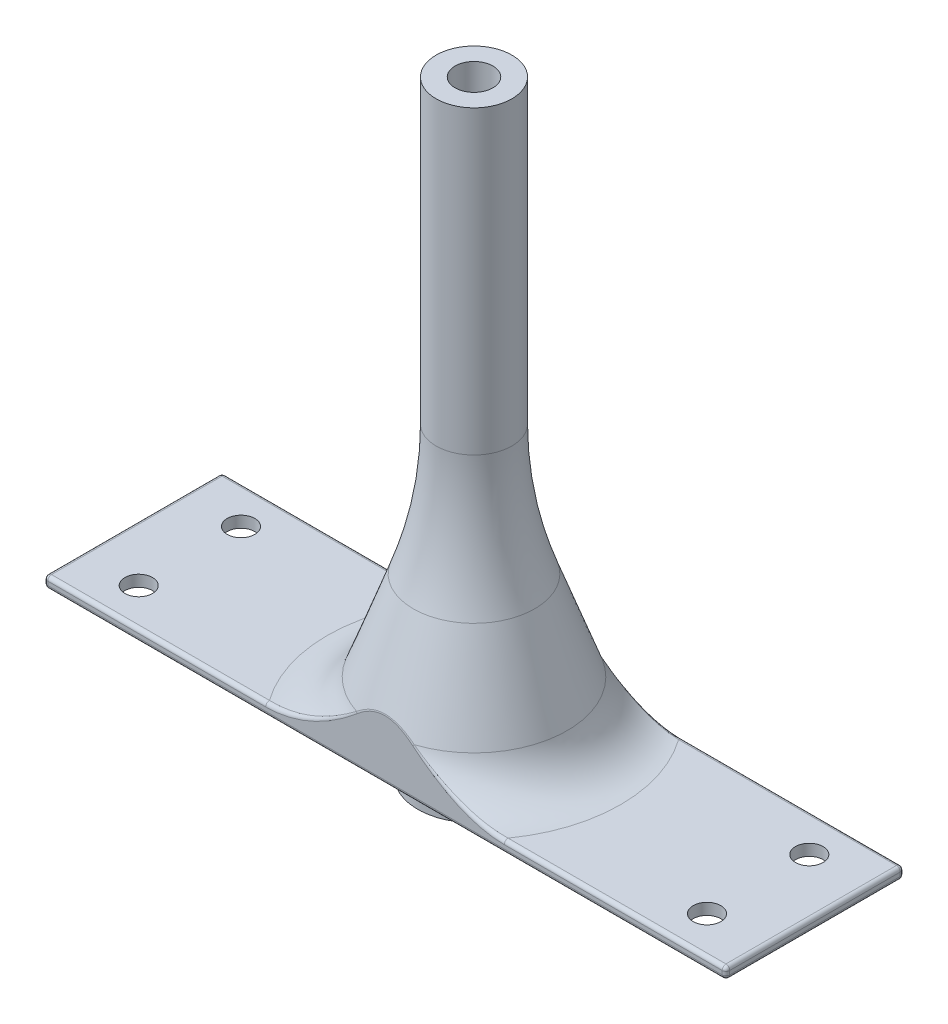
SolidWorks part; units mm, degrees
ref_plane "Alzado" through (0, 0, 0) normal (0, 0, 1) x (1, 0, 0)
ref_plane "Planta" through (0, 0, 0) normal (0, 1, 0) x (1, 0, 0)
ref_plane "Vista lateral" through (0, 0, 0) normal (1, 0, 0) x (0, 0, -1)
sketch "Croquis1" plane through (0, 0, 0) normal (0, 1, 0) x (1, 0, 0)
  circle A0 centre (0, 0) radius 10
  dimension "D1" = 20
extrude "Saliente-Extruir1" add sketch "Croquis1" along normal blind 150 and the other way blind 10
sketch "Croquis5" plane through (0, 150, 0) normal (0, -1, 0) x (1, 0, 0)
  circle A0 centre (0, 0) radius 5
  dimension "D1" = 10
extrude "Cortar-Extruir1" cut sketch "Croquis5" against normal through all both and the other way through all
sketch "Croquis6" plane through (0, 0, 0) normal (0, 1, 0) x (1, 0, 0)
  line L0 (-90, 13.5) -> (-75, 13.5) construction
  line L1 (-90, 23.5) -> (90, 23.5)
  line L2 (-90, 23.5) -> (-90, -23.5)
  line L3 (-90, -23.5) -> (90, -23.5)
  line L4 (90, 23.5) -> (90, -23.5)
  line L5 (-90, 23.5) -> (90, -23.5) construction
  line L6 (-90, -23.5) -> (90, 23.5) construction
  line L7 (-75, 13.5) -> (-75, 23.5) construction
  line L8 (-18.619, 0) -> (0, 0) construction
  line L9 (0, 0) -> (0, 19.4113) construction
  circle A0 centre (-75, 13.5) radius 3.65
  circle A1 centre (75, 13.5) radius 3.65
  circle A2 centre (75, -13.5) radius 3.65
  circle A3 centre (-75, -13.5) radius 3.65
  circle A4 centre (0, 0) radius 5
  point P0 (0, 0)
  dimension "D5" = 7.3
  dimension "D1" = 47
  dimension "D2" = 180
  dimension "D3" = 15
  dimension "D4" = 10
  dimension "D6" = 75
  dimension "D7" = 13.5
extrude "Saliente-Extruir2" add sketch "Croquis6" along normal blind 3
chamfer "Chaflán1" distance 50 angle 20 1 edges at (0, 3, 10) first distance on face at (0, 3, 10)
fillet "Redondeo1" radius 15 2 edges at (-28.1985, 3, 0) (28.1985, 3, 0)
fillet "Redondeo2" radius 1 20 edges at (20.3072, 5.0933, -23.5) (0.5986, 15.8881, -23.5) (90, 1.5, -23.5) (60.375, 3, -23.5) (90, 0, 0) (0, 0, -23.5) (-23.2501, 4.1023, -23.5) (90, 3, 0) (90, 1.5, 23.5) (0, 0, 23.5) (-90, 0, 0) (-90, 1.5, -23.5) (-60.375, 3, -23.5) (60.375, 3, 23.5) (-90, 1.5, 23.5) (-90, 3, 0) (23.2501, 4.1023, 23.5) (-60.375, 3, 23.5) (-0.5986, 15.8881, 23.5) (-20.3072, 5.0933, 23.5)
sketch "Croquis7" plane through (0, -10, 0) normal (0, -1, 0) x (1, 0, 0)
  circle A0 centre (0, 0) radius 5
  circle A1 centre (0, 0) radius 14.85
  dimension "D1" = 29.7
  dimension "D2" = 10
extrude "Saliente-Extruir3" add sketch "Croquis7" against normal blind 10
fillet "Redondeo4" radius 3 1 edges at (0, 0, -14.85)
fillet "Redondeo5" radius 100 1 edges at (0, 53, 10)
sketch "Croquis8" plane through (0, -10, 0) normal (0, -1, 0) x (1, 0, 0)
  circle A0 centre (0, 0) radius 5
extrude "Saliente-Extruir4" add sketch "Croquis8" against normal blind 10
